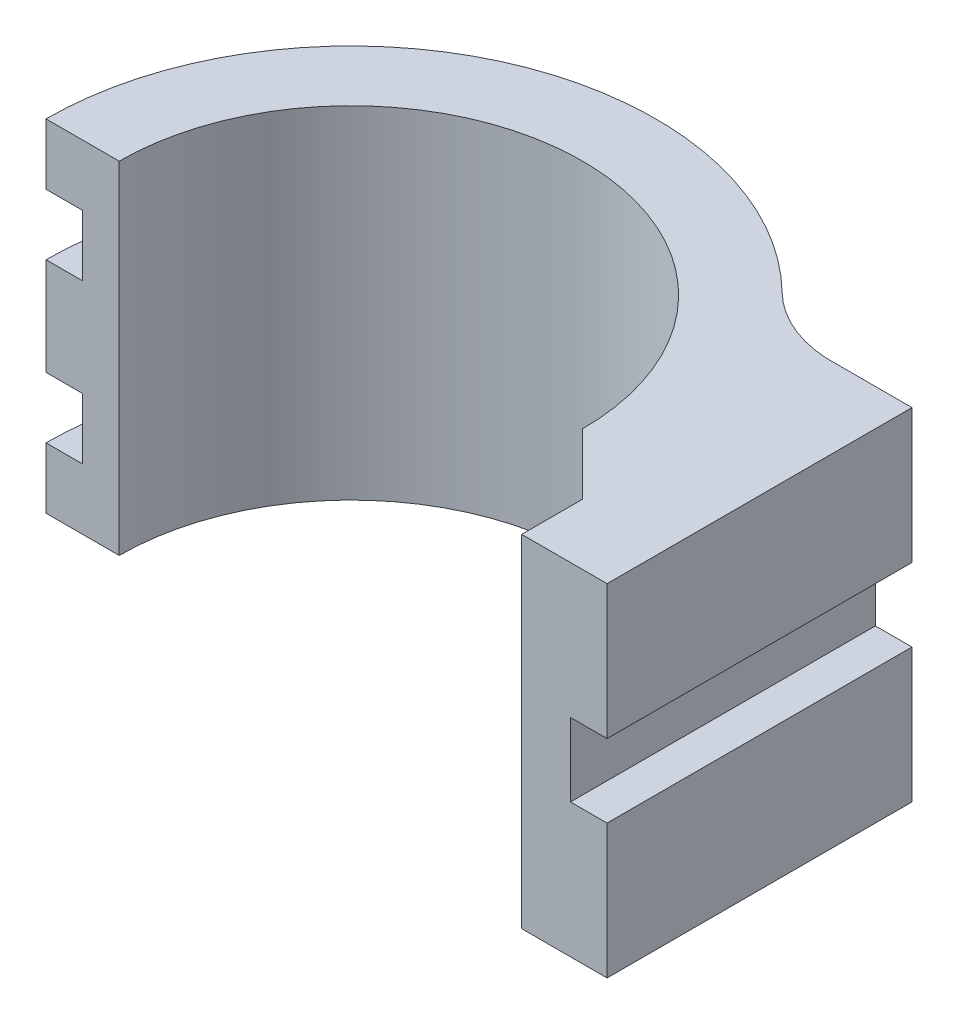
SolidWorks part; units mm, degrees
ref_plane "Alzado" through (0, 0, 0) normal (0, 0, 1) x (1, 0, 0)
ref_plane "Planta" through (0, 0, 0) normal (0, 1, 0) x (1, 0, 0)
ref_plane "Vista lateral" through (0, 0, 0) normal (1, 0, 0) x (0, 0, -1)
sketch "Croquis1" plane through (0, 0, 0) normal (0, 0, 1) x (1, 0, 0)
  line L0 (0, 0) -> (0, 28)
  line L1 (0, 28) -> (25, 28)
  line L2 (25, 28) -> (25, 23)
  line L3 (25, 23) -> (22, 23)
  line L4 (22, 23) -> (22, 18)
  line L5 (22, 18) -> (25, 18)
  line L6 (0, 0) -> (25, 0)
  line L7 (25, 0) -> (25, 5)
  line L8 (25, 5) -> (22, 5)
  line L9 (22, 5) -> (22, 10)
  line L10 (22, 10) -> (25, 10)
  line L11 (25, 10) -> (25, 18)
revolve "Revolución1" add sketch "Croquis1" angle 180 about L0
sketch "Croquis2" plane through (0, 28, 0) normal (0, 1, 0) x (1, 0, 0)
  line L0 (-25, 0) -> (25, 0) construction
  circle A0 centre (0, 0) radius 19
extrude "Cortar-Extruir1" cut sketch "Croquis2" against normal blind 29
sketch "Croquis3" plane through (0, 0, 0) normal (0, 0, 1) x (1, 0, 0)
  line L0 (25, 28) -> (24, 28)
  line L1 (19, 28) -> (25, 28) construction
  line L2 (24, 28) -> (24, 0)
  line L3 (25, 0) -> (19, 0) construction
  line L4 (24, 0) -> (31, 0)
  line L5 (31, 0) -> (31, 28)
  line L6 (31, 28) -> (25, 28)
extrude "Saliente-Extruir1" add sketch "Croquis3" against normal blind 15
sketch "Croquis4" plane through (0, 0, 0) normal (0, 0, 1) x (1, 0, 0)
  line L0 (31, 0) -> (24, 0)
  line L1 (31, 0) -> (19, 0) construction
  line L2 (24, 0) -> (24, 28)
  line L3 (19, 28) -> (31, 28) construction
  line L4 (24, 28) -> (31, 28)
  line L5 (31, 28) -> (31, 0)
extrude "Saliente-Extruir2" add sketch "Croquis4" along normal blind 10
chamfer "Chaflán1" distance 5 angle 45 1 edges at (24, 2.5, 0)
fillet "Redondeo1" radius 10 3 edges at (24, 25.5, -7) (24, 14, -7) (24, 2.5, -7)
sketch "Croquis5" plane through (0, 0, -15) normal (0, 0, -1) x (-1, 0, 0)
  line L0 (-31, 14) -> (-31, 11)
  line L1 (-31, 0) -> (-31, 28) construction
  line L2 (-31, 11) -> (-28, 11)
  line L3 (-28, 11) -> (-28, 17)
  line L4 (-28, 17) -> (-31, 17)
  line L5 (-31, 17) -> (-31, 14)
extrude "Cortar-Extruir2" cut sketch "Croquis5" against normal blind 40
